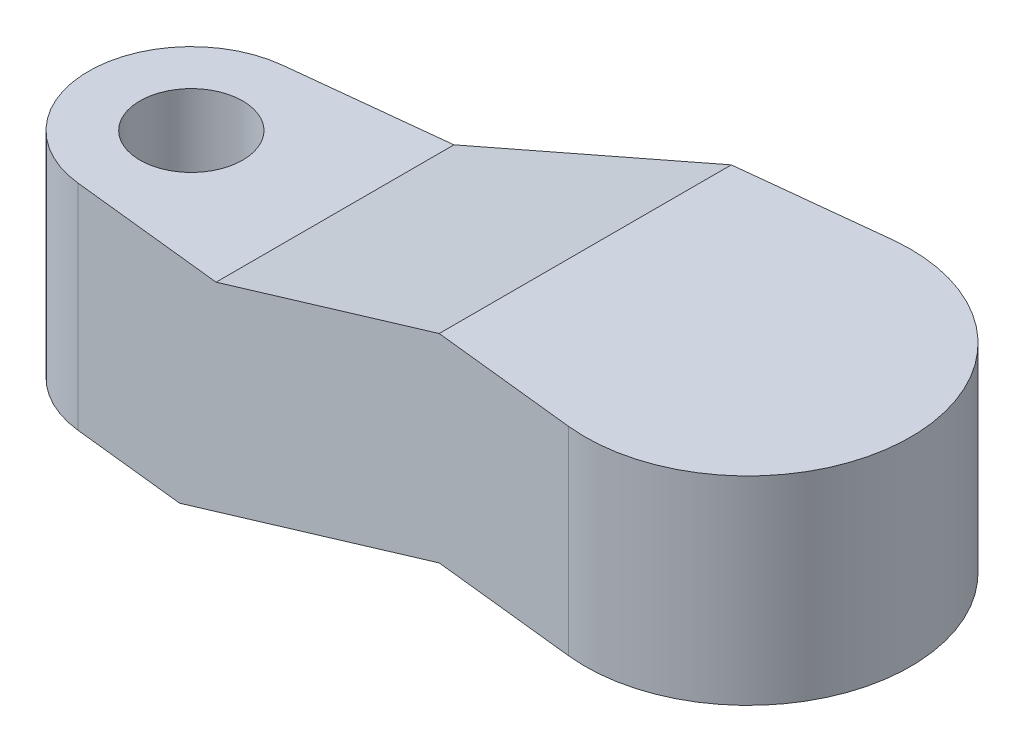
SolidWorks part; units mm, degrees
ref_plane "Front Plane" through (0, 0, 0) normal (0, 0, 1) x (1, 0, 0)
ref_plane "Top Plane" through (0, 0, 0) normal (0, 1, 0) x (1, 0, 0)
ref_plane "Right Plane" through (0, 0, 0) normal (1, 0, 0) x (0, 0, -1)
sketch "Sketch1" plane through (0, 0, 0) normal (0, 1, 0) x (1, 0, 0)
  line L0 (-16.5731, 2.9826) -> (-0.5115, 4.7224)
  line L1 (-16.5731, -2.9826) -> (-0.5115, -4.7224)
  arc A0 (-16.5731, 2.9826) -> (-16.5731, -2.9826) centre (-16.25, 0) ccw
  arc A1 (-0.5115, 4.7224) -> (-0.5115, -4.7224) centre (0, 0) cw
  point P6 (0, 0)
  point P7 (0, 0)
  point P8 (4.75, 0)
  point P9 (-19.25, 0)
  point P10 (0, 0)
  dimension "D1" = 3
  dimension "D2" = 4.75
  dimension "D3" = 24
extrude "Boss-Extrude1" add sketch "Sketch1" along normal blind 9 contours L0 A1 L1 A0
sketch "Sketch2" plane through (0, 0, 0) normal (0, 0, 1) x (1, 0, 0)
  line L0 (-4.75, 9) -> (-12.0547, 6.25)
  line L1 (-16.5731, 9) -> (-0.5115, 9) construction
  line L2 (-12.0547, 6.25) -> (-19.25, 6.25)
  line L3 (-19.25, 9) -> (-19.25, 0) construction
  line L4 (-19.25, 6.25) -> (-19.25, 9)
  line L5 (-16.5731, 9) -> (-19.25, 9) construction
  line L6 (-19.25, 9) -> (-4.75, 9)
  line L7 (-13.25, 0) -> (-4.75, 3.2)
  line L8 (-16.5731, 0) -> (-0.5115, 0) construction
  line L9 (-4.75, 3.2) -> (4.75, 3.2)
  line L10 (4.75, 0) -> (4.75, 9) construction
  line L11 (4.75, 3.2) -> (4.75, 0)
  line L12 (4.75, 0) -> (-13.25, 0)
  point P14 (0, 0)
  point P20 (0.4775, 3.2)
  point P22 (-1.0912, 3.2)
  point P23 (-9.4985, 0)
  point P24 (-10.9212, 6.25)
  point P25 (-4.6628, 9)
  dimension "D1" = 5.8
  dimension "D2" = 6.25
  dimension "D3" = 9.5
  dimension "D4" = 6
extrude "Cut-Extrude1" cut sketch "Sketch2" against normal through all both and the other way through all
sketch "Sketch3" plane through (0, 3.2, 0) normal (0, -1, 0) x (1, 0, 0)
  circle A0 centre (0, 0) radius 2
  dimension "D1" = 4
extrude "Cut-Extrude2" cut sketch "Sketch3" against normal blind 2
sketch "Sketch4" plane through (0, 0, 0) normal (0, -1, 0) x (1, 0, 0)
  circle A0 centre (-16.25, 0) radius 1.5
  arc A1 (-16.5731, 2.9826) -> (-16.5731, -2.9826) centre (-16.25, 0) ccw construction
  point P2 (0, 0)
  dimension "D1" = 3
extrude "Cut-Extrude3" cut sketch "Sketch4" against normal through all
